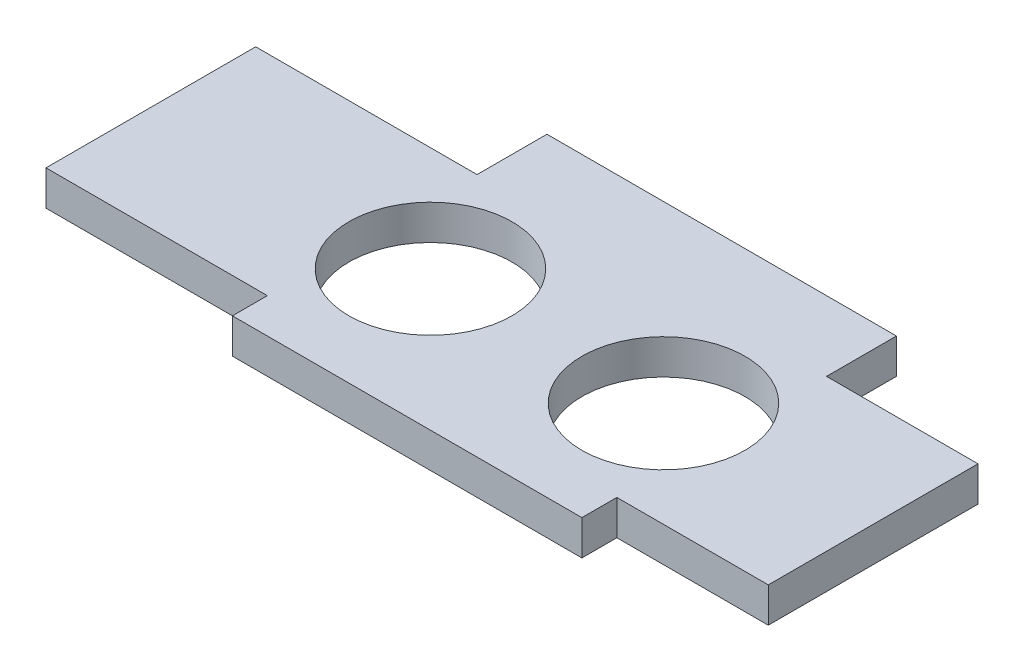
SolidWorks part; units mm, degrees
ref_plane "Front Plane" through (0, 0, 0) normal (0, 0, 1) x (1, 0, 0)
ref_plane "Top Plane" through (0, 0, 0) normal (0, 1, 0) x (1, 0, 0)
ref_plane "Right Plane" through (0, 0, 0) normal (1, 0, 0) x (0, 0, -1)
sketch "Sketch1" plane through (0, 0, 0) normal (0, 1, 0) x (1, 0, 0)
  line L0 (-3, 0) -> (-3, 50000) construction
  line L1 (3, 0) -> (3, 50000) construction
  line L2 (5, 0) -> (5, 50000) construction
  line L3 (-30.5, 9) -> (5.5, 9)
  line L4 (-30.5, 9) -> (-30.5, -9)
  line L5 (-30.5, -9) -> (5.5, -9)
  line L6 (5.5, 9) -> (5.5, -9) construction
  line L7 (-5, 0) -> (-5, 50000) construction
  line L9 (25.5, 9) -> (-10.5, 9)
  line L10 (25.5, 9) -> (25.5, -9)
  line L11 (25.5, -9) -> (-10.5, -9)
  line L12 (-10.5, 9) -> (-10.5, -9) construction
  line L13 (-30.5, 9) -> (25.5, 9)
  line L14 (-30.5, 9) -> (-30.5, -9)
  line L15 (-30.5, -9) -> (25.5, -9)
  line L16 (25.5, 9) -> (25.5, -9)
  circle A0 centre (0, 0) radius 3 construction
  circle A1 centre (-12.5, 0) radius 7
  circle A2 centre (7.5, 0) radius 7
  circle A3 centre (-10, 0) radius 15 construction
  circle A4 centre (10, 0) radius 15 construction
  point P11 (-30.5, 0)
  point P18 (-12.5, 9)
  point P25 (9.3539, 9)
  point P26 (7.5, 9)
  point P28 (25.5, 0)
  dimension "D1" = 6
  dimension "D2" = 36
  dimension "D5" = 14
  dimension "D6" = 14
  dimension "D9" = 2
  dimension "D7" = 2
  dimension "D8" = 7
  dimension "D10" = 12.5
  dimension "D3" = 7
  dimension "D4" = 18
  dimension "D11" = 7.5
  dimension "D12" = 36
extrude "BaseShape" add sketch "Sketch1" along normal blind 3 contours A2 | L14 L13 L16 L15 | A1 region at (7.5, 0, 0)
sketch "Sketch2" plane through (0, 0, 0) normal (0, -1, 0) x (1, 0, 0)
  line L0 (-30.5, -9) -> (25.5, -9) construction
  line L1 (-30.5, -9) -> (-36.5, -9)
  line L2 (-30.5, -9) -> (-30.5, 9)
  line L3 (-30.5, 9) -> (-36.5, 9)
  line L4 (-36.5, -9) -> (-36.5, 9)
  line L5 (-17.5, -9) -> (12.5, -9)
  line L6 (-17.5, -9) -> (-17.5, -15)
  line L7 (-17.5, -15) -> (12.5, -15)
  line L8 (12.5, -9) -> (12.5, -15)
  line L9 (-30.5, -9) -> (-17.5, -9) construction
  line L10 (12.5, -9) -> (25.5, -9) construction
  line L11 (-17.5, 9) -> (-17.5, 12)
  line L12 (-30.5, 9) -> (25.5, 9) construction
  line L13 (-17.5, 12) -> (12.5, 12)
  line L14 (12.5, 12) -> (12.5, 9)
  line L15 (12.5, 9) -> (-17.5, 9)
  dimension "D1" = 6
  dimension "D2" = 6
  dimension "D3" = 30
  dimension "D4" = 3
extrude "FingerJoints" add sketch "Sketch2" against normal up to surface (3 mm away) up to face at (-2.5, 3, 0)
